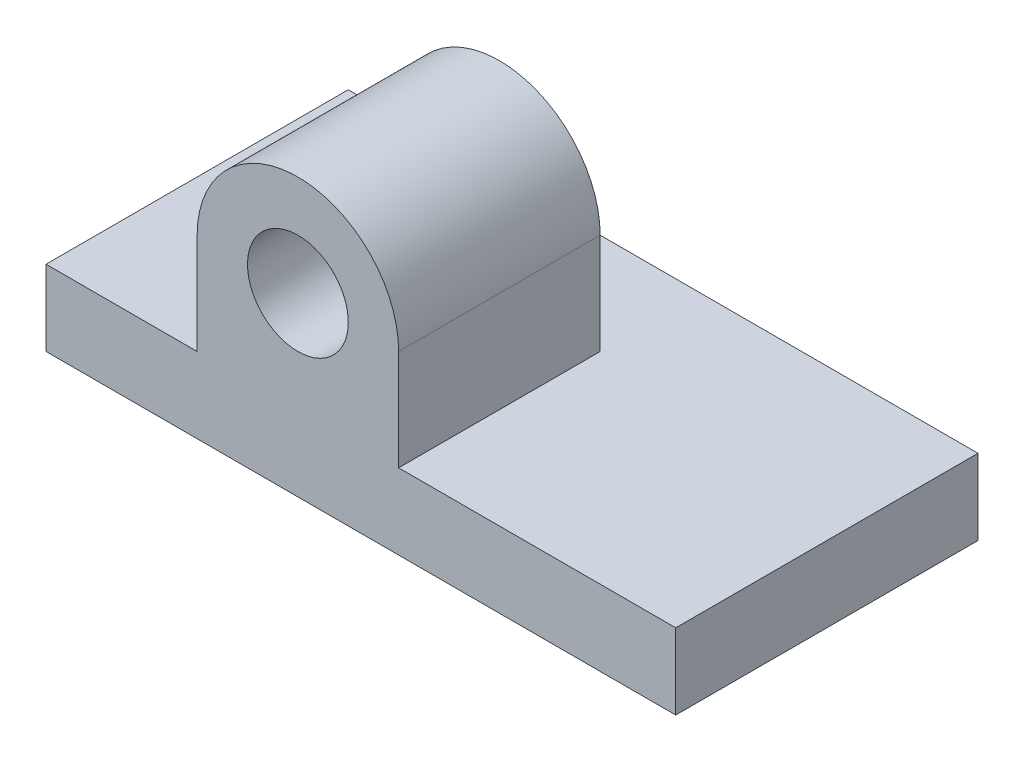
SolidWorks part; units mm, degrees
ref_plane "Front Plane" through (0, 0, 0) normal (0, 0, 1) x (1, 0, 0)
ref_plane "Top Plane" through (0, 0, 0) normal (0, 1, 0) x (1, 0, 0)
ref_plane "Right Plane" through (0, 0, 0) normal (1, 0, 0) x (0, 0, -1)
sketch "Sketch1" plane through (0, 0, 0) normal (0, 0, 1) x (1, 0, 0)
  line L0 (30, 15) -> (30, 35)
  line L1 (0, 0) -> (125, 0)
  line L2 (0, 0) -> (0, 15)
  line L3 (0, 15) -> (125, 15)
  line L4 (125, 0) -> (125, 15)
  line L5 (70, 35) -> (70, 15)
  arc A1 (30, 35) -> (70, 35) centre (50, 35) cw
  circle A2 centre (50, 35) radius 10
  dimension "D5" = 20
  dimension "D6" = 20
  dimension "D1" = 125
  dimension "D2" = 15
  dimension "D3" = 35
  dimension "D4" = 50
extrude "Boss-Extrude1" add sketch "Sketch1" against normal blind 60 contours L1 L4 L3 L2 region at (62.5, 7.5, 0)
extrude "Boss-Extrude2" add sketch "Sketch1<3>" against normal blind 40 contours A1 L0 L3 L5 A2 region at (30.5657, 25, 0)
sketch "Sketch1<3>" plane through (0, 0, 0) normal (0, 0, 1) x (1, 0, 0) same geometry as "Sketch1"
